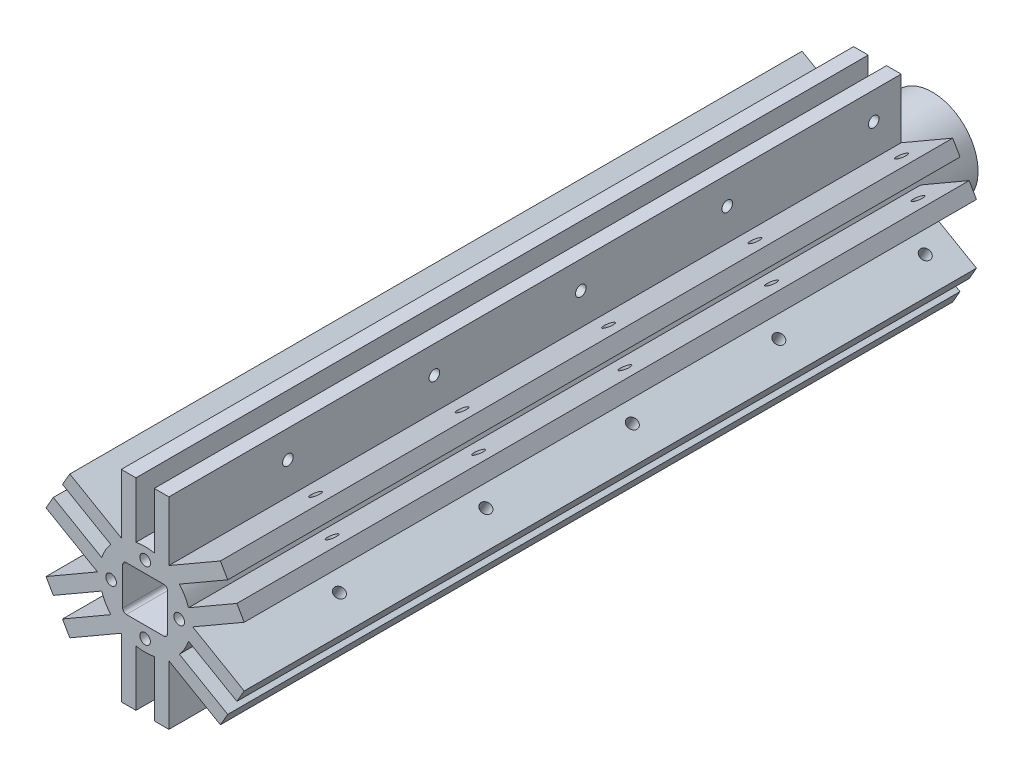
SolidWorks part; units mm, degrees
ref_plane "Front Plane" through (0, 0, 0) normal (0, 0, 1) x (1, 0, 0)
ref_plane "Top Plane" through (0, 0, 0) normal (0, 1, 0) x (1, 0, 0)
ref_plane "Right Plane" through (0, 0, 0) normal (1, 0, 0) x (0, 0, -1)
sketch "Sketch1" plane through (0, 0, 0) normal (0, 0, 1) x (1, 0, 0)
  circle A0 centre (0, 0) radius 12.5
  dimension "D2" = 25
extrude "Boss-Extrude1" add sketch "Sketch1" along normal mid plane 200
sketch "Sketch4" plane through (0, 0, 100) normal (0, 0, 1) x (1, 0, 0)
  line L0 (8.25, 0) -> (-8.25, 0) construction
  line L2 (-6.5, 0) -> (-2.5, 0)
  line L3 (0, 0) -> (0, 15.8331) construction
  line L4 (-6.5, 0) -> (-6.5, 27.5)
  line L5 (-6.5, 27.5) -> (-2.5, 27.5)
  line L6 (-2.5, 0) -> (-2.5, 27.5)
  line L7 (0, -8.25) -> (0, 8.25) construction
  line L8 (6.5, 27.5) -> (2.5, 27.5)
  line L9 (2.5, 0) -> (2.5, 27.5)
  line L10 (6.5, 0) -> (2.5, 0)
  line L11 (6.5, 0) -> (6.5, 27.5)
  dimension "D1" = 27.5
  dimension "D3" = 2.5
  dimension "D2" = 4
extrude "Boss-Extrude3" add sketch "Sketch4" against normal up to surface (200 mm away) up to face at (12.5, 0, -100)
pattern_circular "CirPattern7" count 6 over 360 about axis through (0, 0, -100) along (0, 0, 1) of "Boss-Extrude3"
sketch "Sketch7" plane through (-6.5, 0, 0) normal (-1, 0, 0) x (0, 0, 1)
  line L0 (-100, 27.5) -> (100, 27.5) construction
  line L1 (-100, 11.2583) -> (-100, 27.5) construction
  circle A0 centre (-92.5, 20) radius 1.45
  circle A1 centre (-52.5, 20) radius 1.45
  circle A2 centre (-12.5, 20) radius 1.45
  circle A3 centre (27.5, 20) radius 1.45
  circle A4 centre (67.5, 20) radius 1.45
  dimension "D1" = 2.9
  dimension "D2" = 7.5
  dimension "D3" = 7.5
  dimension "D4" = 5
extrude "Cut-Extrude2" cut sketch "Sketch7" against normal blind 17
pattern_circular "CirPattern9" count 6 over 360 about axis through (0, 0, 100) along (0, 0, 1) of "Cut-Extrude2"
sketch "Sketch10" plane through (0, 0, -100) normal (0, 0, -1) x (-1, 0, 0)
  circle A0 centre (0, 0) radius 12.5
  dimension "D1" = 25
extrude "Boss-Extrude4" add sketch "Sketch10" along normal blind 15
sketch "Sketch8" plane through (0, 0, 100) normal (0, 0, 1) x (1, 0, 0)
  line L2 (-6.125, 6.125) -> (6.125, 6.125)
  line L3 (-6.125, 6.125) -> (-6.125, -6.125)
  line L4 (-6.125, -6.125) -> (6.125, -6.125)
  line L5 (6.125, 6.125) -> (6.125, -6.125)
  line L6 (-6.125, 6.125) -> (6.125, -6.125) construction
  line L7 (-6.125, -6.125) -> (6.125, 6.125) construction
  point P5 (0, 0)
  point P14 (0, 0)
  dimension "D1" = 12.25
extrude "Cut-Extrude3" cut sketch "Sketch8" against normal up to next
sketch "Sketch9" plane through (0, 0, 100) normal (0, 0, 1) x (1, 0, 0)
  line L0 (29.7723, 0) -> (-29.7723, 0) construction
  line L1 (6.125, -6.125) -> (6.125, 6.125) construction
  circle A0 centre (9.3125, 0) radius 1.45
  circle A1 centre (0, -9.2875) radius 1.45
  circle A2 centre (-9.2875, 0.025) radius 1.45
  circle A3 centre (0.025, 9.3125) radius 1.45
  point P14 (0.0125, 0.0125)
  dimension "D1" = 2.9
  dimension "D2" = 3.1875
  dimension "D3" = 4
extrude "Cut-Extrude4" cut sketch "Sketch9" against normal blind 10
fillet "Fillet1" radius 1 4 edges at (-6.125, 6.125, -7.5) (6.125, 6.125, -7.5) (6.125, -6.125, -7.5) (-6.125, -6.125, -7.5)
equation "\"drumDiameter\"= 25"
equation "\"D2@Sketch1\"=\"drumDiameter\""
equation "\"drumLength\"= 200"
equation "\"D1@Sketch4\"=\"drumDiameter\"*(0.5+\"drumAbove\")"
equation "\"foamThickness\"= 5"
equation "\"D3@Sketch4\"=\"foamThickness\"/2"
equation "\"drumAbove\"= 0.6"
equation "\"D2@Sketch7\"=\"drumDiameter\"*\"drumAbove\"/2"
equation "\"holderThicc\"= 4"
equation "\"D2@Sketch4\"=\"holderThicc\""
equation "\"D1@Boss-Extrude1\"=\"drumLength\""
equation "\"squareBarLength\"= 12.25"
equation "\"D1@Sketch8\"=\"squareBarLength\""
equation "\"D2@Sketch9\"=(\"drumDiameter\"/2-\"squareBarLength\"/2)/2"
equation "\"D1@Sketch10\"=\"drumDiameter\""
